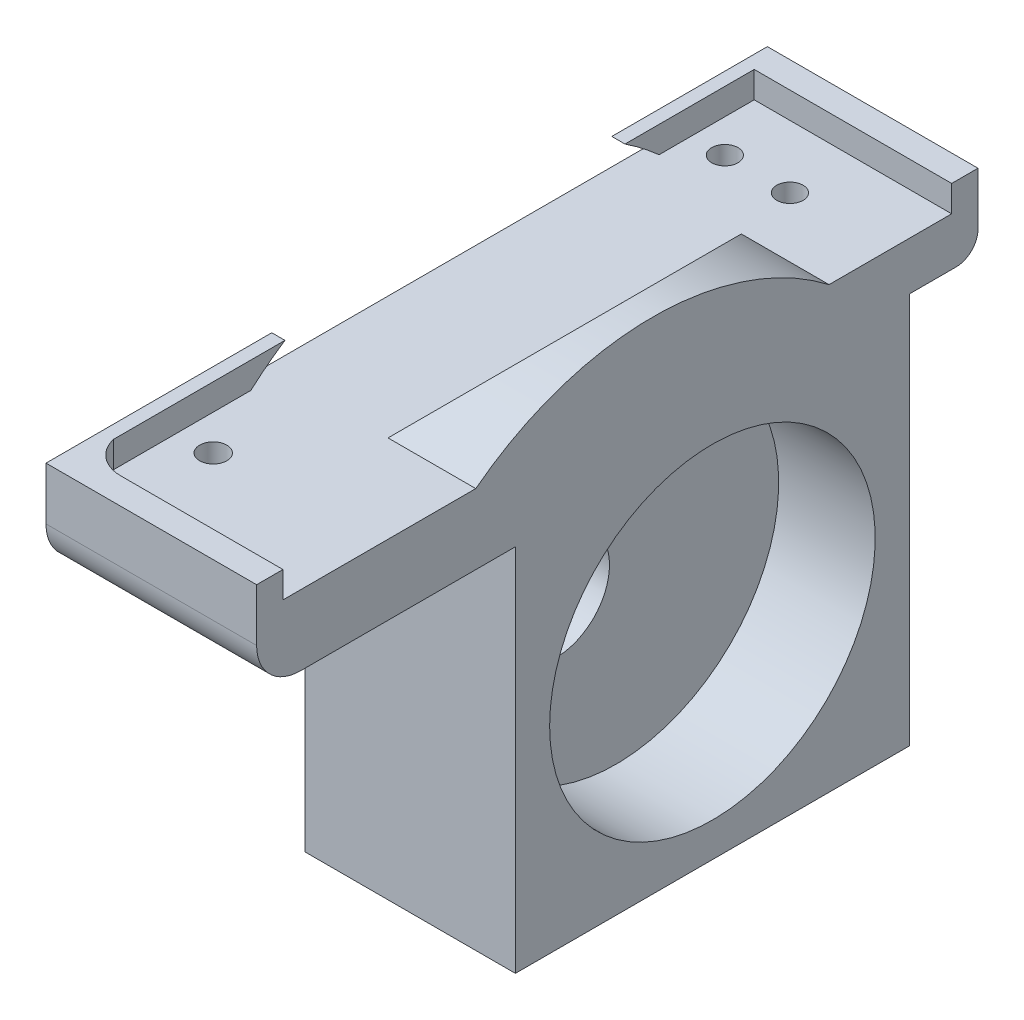
SolidWorks part; units mm, degrees
note: The reader was unsure of these and kept them because the rebuilt part matched: shared geometry of "Sketch1<3>", "Sketch1<4>", "Sketch3<3>", "Sketch3<4>", "Sketch3<5>".
ref_plane "Front Plane" through (0, 0, 0) normal (0, 0, 1) x (1, 0, 0)
ref_plane "Top Plane" through (0, 0, 0) normal (0, 1, 0) x (1, 0, 0)
ref_plane "Right Plane" through (0, 0, 0) normal (1, 0, 0) x (0, 0, -1)
sketch "Sketch1" plane through (4.5882, 0, 0) normal (-1, 0, 0) x (0, 0, 1)
  line L0 (97.7133, 21.2965) -> (97.7133, 24.2965)
  line L1 (97.7133, 24.2965) -> (94.7133, 24.2965)
  line L2 (94.7133, 24.2965) -> (94.7133, 18.2965)
  line L3 (97.2133, 15.7965) -> (102.5258, 15.7965)
  line L4 (102.5258, 15.7965) -> (102.5258, -28.8035)
  line L5 (102.5258, -28.8035) -> (147.4258, -28.8035)
  line L6 (147.4258, -28.8035) -> (147.4258, 13.2965)
  line L7 (147.4258, 13.2965) -> (171.9133, 13.2965)
  line L8 (176.9133, 18.2965) -> (176.9133, 24.2965)
  line L9 (176.9133, 24.2965) -> (173.9133, 24.2965)
  line L10 (173.9133, 24.2965) -> (173.9133, 21.2965)
  line L11 (173.9133, 21.2965) -> (97.7133, 21.2965)
  circle A0 centre (131.8133, -4.8539) radius 3.075
  circle A1 centre (131.8133, -4.8539) radius 6.11
  circle A2 centre (131.8133, -4.8539) radius 3.075 construction
  circle A3 centre (131.8133, -4.8539) radius 6.11 construction
  circle A4 centre (124.9758, -6.3535) radius 18.55
  circle A5 centre (124.9758, -6.3535) radius 18.55 construction
  circle A6 centre (124.9758, -6.3535) radius 22.45
  circle A7 centre (124.9758, -6.3535) radius 22.45 construction
  arc A8 (94.7133, 18.2965) -> (97.2133, 15.7965) centre (97.2133, 18.2965) ccw
  arc A9 (171.9133, 13.2965) -> (176.9133, 18.2965) centre (171.9133, 18.2965) ccw
  circle M19 centre (131.8133, -4.8539) radius 5.25
extrude "Boss-Extrude1" add sketch "Sketch1" along normal up to surface (5.5 mm away) contours L7 A9 L8 L9 L10 L11 L0 L1 L2 A8 L3 L4 A6 L6 | A6 L4 L5 | A6 A4 | A4 A1 | A0 M19 | A1 M19 | A6 L5 L6
extrude "Boss-Extrude2" add sketch "Sketch1<3>" against normal up to surface (6 mm away) contours L7 A9 L8 L9 L10 L11 L0 L1 L2 A8 L3 L4 A6 L6 | A6 L5 L6 | A6 A4 | A4 A1
sketch "Sketch1<3>" plane through (4.5882, 0, 0) normal (-1, 0, 0) x (0, 0, 1) same geometry as "Sketch1"
extrude "Boss-Extrude3" add sketch "Sketch1<4>" against normal up to surface (17 mm away) contours L7 A9 L8 L9 L10 L11 L0 L1 L2 A8 L3 L4 A6 L6 | A6 L5 L6 | A6 L4 L5 | A6 A4
sketch "Sketch1<4>" plane through (4.5882, 0, 0) normal (-1, 0, 0) x (0, 0, 1) same geometry as "Sketch1"
sketch "Sketch2" plane through (21.5882, 0, 0) normal (1, 0, 0) x (0, 0, -1)
  line L0 (-97.7133, 21.2965) -> (-173.9133, 21.2965) construction
  line L1 (-173.9133, 21.2965) -> (-97.7133, 21.2965) construction
  line L2 (-111.6848, 21.2965) -> (-151.9417, 21.2965)
  arc A0 (-111.6848, 21.2965) -> (-151.9417, 21.2965) centre (-131.8133, -4.8539) ccw
  arc A1 (-111.6848, 21.2965) -> (-151.9417, 21.2965) centre (-131.8133, -4.8539) ccw construction
  line M10 (-97.7133, 21.2965) -> (-173.9133, 21.2965)
extrude "Boss-Extrude4" add sketch "Sketch2" against normal blind 10 contours A0 M10
draft "Draft1" type of draft neutral plane draft angle 45 faces to draft 1 face at (11.5882, 24.7213, 131.8133) neutral plane through (-98.7712, 21.2965, 0) neutral plane normal (0, 1, 0) parameters "D1"=45
sketch "Sketch3" plane through (0, 21.2965, 0) normal (0, 1, 0) x (1, 0, 0)
  line L0 (141.4382, -106.5651) -> (144.2882, -108.2106) construction
  line L1 (2.8791, -108.1417) -> (5.7291, -106.4962)
  line L2 (5.7291, -106.4962) -> (5.7291, -103.2053)
  line L3 (5.7291, -103.2053) -> (2.8791, -101.5599)
  line L4 (2.8791, -101.5599) -> (0.0291, -103.2053)
  line L5 (0.0291, -103.2053) -> (0.0291, -106.4962)
  line L6 (0.0291, -106.4962) -> (2.8791, -108.1417)
  line L7 (10.2973, -108.1417) -> (13.1473, -106.4962)
  line L8 (13.1473, -106.4962) -> (13.1473, -103.2053)
  line L9 (13.1473, -103.2053) -> (10.2973, -101.5599)
  line L10 (10.2973, -101.5599) -> (7.4473, -103.2053)
  line L11 (7.4473, -103.2053) -> (7.4473, -106.4962)
  line L12 (7.4473, -106.4962) -> (10.2973, -108.1417)
  line L13 (-0.1777, -163.3808) -> (1.4677, -166.2308)
  line L14 (1.4677, -166.2308) -> (4.7586, -166.2308)
  line L15 (4.7586, -166.2308) -> (6.4041, -163.3808)
  line L16 (6.4041, -163.3808) -> (4.7586, -160.5308)
  line L17 (4.7586, -160.5308) -> (1.4677, -160.5308)
  line L18 (1.4677, -160.5308) -> (-0.1777, -163.3808)
  line L19 (-0.9118, -102.5258) -> (21.5882, -102.5258) construction
  line L20 (-0.9118, -173.9133) -> (21.5882, -173.9133) construction
  line L21 (0.0291, -103.2053) -> (0.0291, -102.5258)
  line L22 (0.0291, -102.5258) -> (5.7291, -102.5258)
  line L23 (5.7291, -102.5258) -> (5.7291, -103.2053)
  line L24 (7.4473, -103.2053) -> (7.4473, -102.5258)
  line L25 (7.4473, -102.5258) -> (13.1473, -102.5258)
  line L26 (13.1473, -102.5258) -> (13.1473, -103.2053)
  line L27 (-0.9118, -173.9133) -> (21.5882, -173.9133) construction
  line L28 (-0.9118, -173.9133) -> (-0.9118, -97.7133) construction
  circle A0 centre (2.8791, -104.8508) radius 1.5
  circle A1 centre (10.2973, -104.8508) radius 1.5
  circle A2 centre (3.1132, -163.3808) radius 1.55
  circle A3 centre (2.8791, -104.8508) radius 1.5 construction
  circle A4 centre (10.2973, -104.8508) radius 1.5 construction
  circle A5 centre (3.1132, -163.3808) radius 1.55 construction
  circle A6 centre (2.8791, -104.8508) radius 2.85 construction
  circle A7 centre (10.2973, -104.8508) radius 2.85 construction
  circle A8 centre (3.1132, -163.3808) radius 2.85 construction
  arc A9 (3.0882, -173.9133) -> (-0.9118, -170.7133) centre (3.0882, -169.8133) cw
  arc A10 (-0.9118, -169.8133) -> (3.0882, -173.8133) centre (3.0882, -169.8133) ccw construction
  line M15 (-0.9118, -97.7133) -> (-0.9118, -173.9133)
  line M16 (-0.9118, -173.9133) -> (21.5882, -173.9133)
extrude "Boss-Extrude5" add sketch "Sketch3<3>" along normal up to surface (3 mm away) contours A9 M16 M15 up to face at (10.3382, 24.2965, 175.4133)
sketch "Sketch3<3>" plane through (0, 21.2965, 0) normal (0, 1, 0) x (1, 0, 0) same geometry as "Sketch3"
sketch "Sketch4" plane through (-0.9118, 0, 0) normal (-1, 0, 0) x (0, 0, 1)
  line L0 (97.7133, 24.2965) -> (112.4418, 24.2965)
  line L1 (170.7133, 24.2965) -> (151.1847, 24.2965)
  line L2 (109.0261, 24.2965) -> (100.8133, 24.2965) construction
  line L3 (169.8133, 24.2965) -> (154.6004, 24.2965) construction
  line L4 (170.7133, 21.2965) -> (97.7133, 21.2965) construction
  line L17 (170.7133, 24.2965) -> (170.7133, 21.2965)
  line L18 (170.7133, 21.2965) -> (97.7133, 21.2965)
  line L19 (97.7133, 21.2965) -> (97.7133, 24.2965)
  line L20 (97.7133, 24.2965) -> (94.7133, 24.2965)
  line L21 (94.7133, 24.2965) -> (94.7133, 18.2965)
  line L22 (97.2133, 15.7965) -> (102.5258, 15.7965)
  line L23 (102.5258, 15.7965) -> (102.5258, -28.8035)
  line L24 (102.5258, -28.8035) -> (147.4258, -28.8035)
  line L25 (147.4258, -28.8035) -> (147.4258, 13.2965)
  line L26 (147.4258, 13.2965) -> (171.9133, 13.2965)
  line L27 (176.9133, 18.2965) -> (176.9133, 24.2965)
  line L28 (176.9133, 24.2965) -> (170.7133, 24.2965)
  line L29 (170.7133, 24.2965) -> (170.7133, 21.2965)
  line L30 (170.7133, 21.2965) -> (97.7133, 21.2965)
  line L31 (97.7133, 21.2965) -> (97.7133, 24.2965)
  line L32 (97.7133, 24.2965) -> (94.7133, 24.2965)
  line L33 (94.7133, 24.2965) -> (94.7133, 18.2965)
  line L34 (97.2133, 15.7965) -> (102.5258, 15.7965)
  line L35 (102.5258, 15.7965) -> (102.5258, -28.8035)
  line L36 (102.5258, -28.8035) -> (147.4258, -28.8035)
  line L37 (147.4258, -28.8035) -> (147.4258, 13.2965)
  line L38 (147.4258, 13.2965) -> (171.9133, 13.2965)
  line L39 (176.9133, 18.2965) -> (176.9133, 24.2965)
  line L40 (176.9133, 24.2965) -> (170.7133, 24.2965)
  arc A0 (108.5505, 21.2965) -> (112.4418, 24.2965) centre (131.8133, -4.8539) cw
  arc A1 (151.1847, 24.2965) -> (155.076, 21.2965) centre (131.8133, -4.8539) cw
  arc A2 (155.076, 21.2965) -> (108.5505, 21.2965) centre (131.8133, -4.8539) ccw construction
  arc A5 (94.7133, 18.2965) -> (97.2133, 15.7965) centre (97.2133, 18.2965) ccw
  arc A6 (171.9133, 13.2965) -> (176.9133, 18.2965) centre (171.9133, 18.2965) ccw
  arc A7 (94.7133, 18.2965) -> (97.2133, 15.7965) centre (97.2133, 18.2965) ccw
  arc A8 (171.9133, 13.2965) -> (176.9133, 18.2965) centre (171.9133, 18.2965) ccw
  line M3 (170.7133, 24.2965) -> (170.7133, 21.2965)
  line M4 (170.7133, 21.2965) -> (97.7133, 21.2965)
  line M5 (97.7133, 21.2965) -> (97.7133, 24.2965)
  line M6 (97.7133, 24.2965) -> (94.7133, 24.2965)
  line M7 (94.7133, 24.2965) -> (94.7133, 18.2965)
  arc M8 (94.7133, 18.2965) -> (97.2133, 15.7965) centre (97.2133, 18.2965) ccw
  line M9 (97.2133, 15.7965) -> (102.5258, 15.7965)
  line M10 (102.5258, 15.7965) -> (102.5258, -28.8035)
  line M11 (102.5258, -28.8035) -> (147.4258, -28.8035)
  line M12 (147.4258, -28.8035) -> (147.4258, 13.2965)
  line M13 (147.4258, 13.2965) -> (171.9133, 13.2965)
  arc M14 (171.9133, 13.2965) -> (176.9133, 18.2965) centre (171.9133, 18.2965) ccw
  line M15 (176.9133, 18.2965) -> (176.9133, 24.2965)
  line M16 (176.9133, 24.2965) -> (170.7133, 24.2965)
  circle M17 centre (131.8133, -4.8539) radius 3.075
  dimension "D1" = 0
extrude "Boss-Extrude6" add sketch "Sketch4" along normal blind 1.5 contours L30 M16 M3 M4 M5 M6 M7 M8 M9 M10 M11 M12 M13 M14 M15 M17 | L30 A0 L0 M5 | L1 A1 M4 M3
extrude "Cut-Extrude1" cut sketch "Sketch3" against normal blind 11 contours A0 | A1 | A2
extrude "Cut-Extrude2" cut sketch "Sketch3<4>" along normal up to surface (2.6 mm away) from surface contours L25 L10 L11 L12 L7 L8 L9 A1 | L26 L25 L9 | L25 L24 L10 | L22 L4 L5 L6 L1 L2 L3 A0 | L23 L22 L3 | L22 L21 L4
sketch "Sketch3<4>" plane through (0, 21.2965, 0) normal (0, 1, 0) x (1, 0, 0) same geometry as "Sketch3"
extrude "Cut-Extrude3" cut sketch "Sketch3<5>" along normal up to surface (2.5 mm away) from surface at -8 contours L17 L18 L13 L14 L15 L16 A2 starting at face at (1.5632, 13.2965, 163.3808)
sketch "Sketch3<5>" plane through (0, 21.2965, 0) normal (0, 1, 0) x (1, 0, 0) same geometry as "Sketch3"
